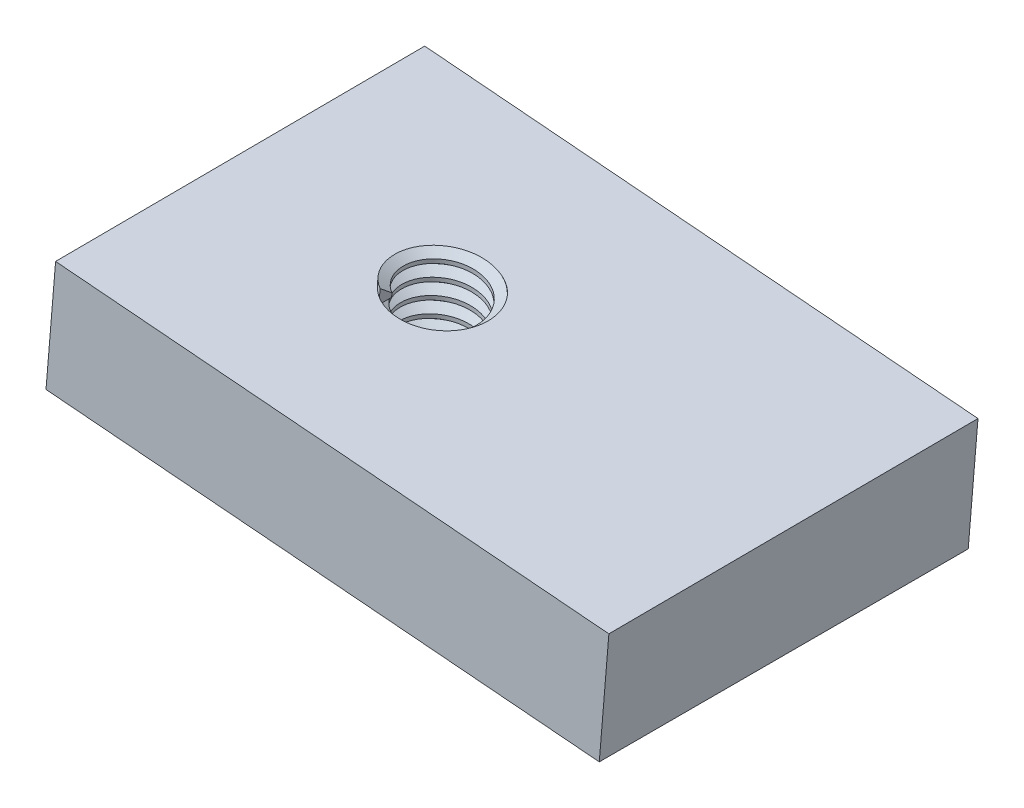
SolidWorks part; units mm, degrees
ref_plane "Front Plane" through (0, 0, 0) normal (0, 0, 1) x (1, 0, 0)
ref_plane "Top Plane" through (0, 0, 0) normal (0, 1, 0) x (1, 0, 0)
ref_plane "Right Plane" through (0, 0, 0) normal (1, 0, 0) x (0, 0, -1)
ref_plane "Plane1" through (-1.3154, -15.8621, 0) normal (-0.0826, -0.9966, 0) x (0.9966, -0.0826, 0)
sketch "Sketch1" plane through (-1.3154, -15.8621, 0) normal (-0.0826, -0.9966, 0) x (0.9966, -0.0826, 0)
  line L0 (-9.1777, 0) -> (-9.1777, 10)
  line L1 (-9.1777, 10) -> (-24.2253, 10)
  line L2 (-24.2253, 10) -> (-24.2253, 0)
  line L3 (-24.2253, 0) -> (-9.1777, 0)
extrude "Boss-Extrude1" add sketch "Sketch1" against normal blind 3.2038
draft "Draft1" type of draft neutral plane draft angle 0.326 faces to draft 1 face at (-17.6949, -11.289, 5) neutral plane through (-25.193, -10.6672, 0) neutral plane normal (0, 0, -1) reverse direction yes parameters "D1"=0.326
ref_plane "Plane2" through (-1.0524, -12.6904, 0) normal (0.0826, 0.9966, 0) x (0.9966, -0.0826, 0)
hole_wizard "#2 Clearance Hole1" positions "Sketch3" profile "Sketch2" hole size "#2" standard "ANSI Inch"
sketch "Sketch3" plane through (-1.0524, -12.6904, 0) normal (0.0826, 0.9966, 0) x (0.9966, -0.0826, 0)
  point P0 (-18.7253, -5)
sketch "Sketch2" plane through (-19.7136, -11.143, 5) normal (0, 0, 1) x (-0.9966, 0.0826, 0)
  line L0 (0, 0) -> (0, 4.4218)
  line L1 (0, 4.4218) -> (1.25, 4.4218)
  line L2 (1.25, 4.4218) -> (1.25, 0)
  line L5 (1.25, 0) -> (0, 0)
  line L11 (0, -6.35) -> (0, 107.95) construction
  dimension "Thru Hole Dia." = 2.5
  dimension "Thru Hole Depth" = 4.4218
thread "螺纹线1" pitch 0.45 method extrude profile "螺纹线轮廓1" start angle 0, offset 0, length 3, pitch 0.45, diameter 2.5
ref_plane "基准面1" through (-18.7309, -14.4179, 5) normal (0, 0, 1) x (0.9966, -0.0826, 0)
sketch "螺纹线轮廓1" plane through (-18.7309, -14.4179, 5) normal (0, 0, 1) x (0.9966, -0.0826, 0)
  line L0 (0, 0) -> (0, 0.45) construction
  line L11 (0, 0) -> (0, 0.3937)
  line L12 (0, 0.3937) -> (-0.2436, 0.2531)
  line L13 (-0.2436, 0.2531) -> (-0.2436, 0.1406)
  line L15 (-0.2436, 0.1406) -> (0, 0)
  line L17 (-0.2436, 0.1969) -> (0, 0.1969) construction
  point P2 (0, 0)
  dimension "Pitch" = 0.45
  dimension "Profile_Angle" = 60
  dimension "Profile_Land" = 0.1125
  dimension "Profile_Height" = 0.2436
